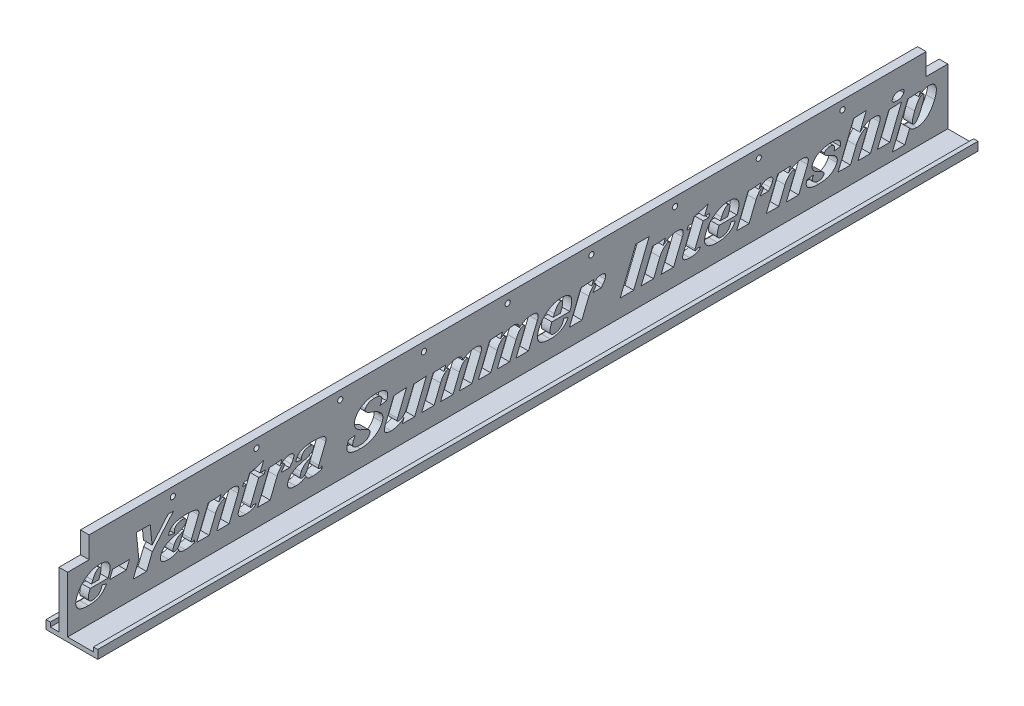
SolidWorks part; units mm, degrees
material "Acrylic (Medium-high impact)"
ref_plane "Front Plane" through (0, 0, 0) normal (0, 0, 1) x (1, 0, 0)
ref_plane "Top Plane" through (0, 0, 0) normal (0, 1, 0) x (1, 0, 0)
ref_plane "Right Plane" through (0, 0, 0) normal (1, 0, 0) x (0, 0, -1)
sketch "Sketch1" plane through (0, 0, 0) normal (0, 0, 1) x (1, 0, 0)
  line L0 (0, 10) -> (0, 0)
  line L1 (0, 0) -> (60, 0)
  line L2 (60, 0) -> (60, 10)
  line L3 (60, 10) -> (55, 10)
  line L4 (55, 10) -> (55, 5)
  line L5 (55, 5) -> (25, 5)
  line L6 (25, 5) -> (25, 95)
  line L7 (25, 95) -> (15, 95)
  line L8 (15, 95) -> (15, 5)
  line L9 (15, 5) -> (5, 5)
  line L10 (5, 5) -> (5, 10)
  line L11 (5, 10) -> (0, 10)
  dimension "D1" = 10
  dimension "D2" = 10
  dimension "D3" = 5
  dimension "D4" = 5
  dimension "D5" = 5
  dimension "D6" = 10
  dimension "D7" = 60
  dimension "D8" = 95
  dimension "D9" = 5
extrude "Boss-Extrude1" add sketch "Sketch1" along normal blind 1020
sketch "Sketch2" plane through (25, 0, 0) normal (1, 0, 0) x (0, 0, -1)
  line L0 (-1052.1126, 85) -> (45.5589, 85) construction
  line L1 (-1020, 95) -> (-995, 95)
  line L2 (-1020, 95) -> (-1020, 70)
  line L3 (-1020, 70) -> (-995, 70)
  line L4 (-995, 95) -> (-995, 70)
  line L5 (0, 95) -> (-25, 95)
  line L6 (0, 95) -> (0, 70)
  line L7 (0, 70) -> (-25, 70)
  line L8 (-25, 95) -> (-25, 70)
  line L9 (-1020, 95) -> (0, 95) construction
  dimension "D1" = 25
  dimension "D2" = 25
  dimension "D3" = 25
  dimension "D4" = 25
  dimension "D5" = 10
extrude "Cut-Extrude1" cut sketch "Sketch2" against normal blind 10
sketch "Sketch3" plane through (25, 0, 0) normal (1, 0, 0) x (0, 0, -1)
  line L0 (-995, 70) -> (-995, 95) construction
  line L1 (-995, 95) -> (-25, 95) construction
  circle A0 centre (-898, 85) radius 3
  dimension "D3" = 6
  dimension "D1" = 97
  dimension "D2" = 10
extrude "Cut-Extrude2" cut sketch "Sketch3" against normal blind 10
pattern_linear "LPattern1" count 9 spacing 97 along (0, 0, -1) of "Cut-Extrude2"
sketch "Sketch4" plane through (25, 0, 0) normal (1, 0, 0) x (0, 0, -1)
  text T0 "e-Yantra Summer Internship    Programme 2018 " font "Britannic Bold" height 45
extrude "Cut-Extrude3" cut sketch "Sketch4" against normal blind 10
